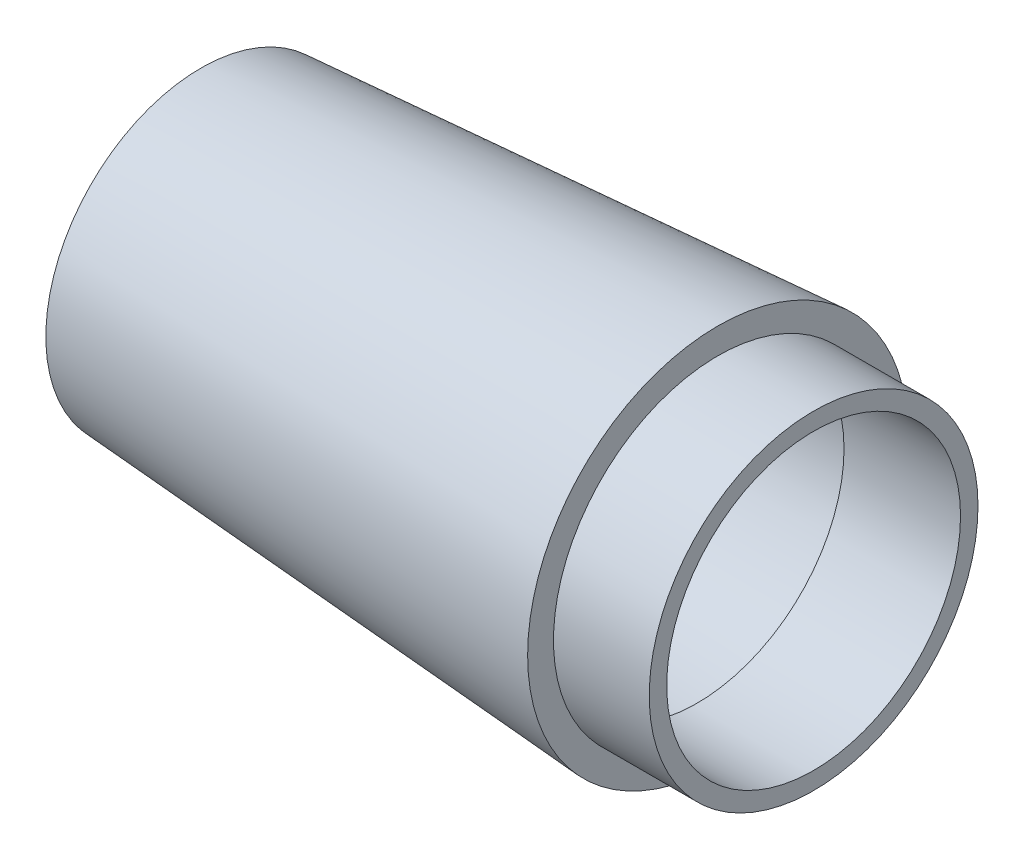
SolidWorks part; units mm, degrees
ref_plane "Front Plane" through (0, 0, 0) normal (0, 0, 1) x (1, 0, 0)
ref_plane "Top Plane" through (0, 0, 0) normal (0, 1, 0) x (1, 0, 0)
ref_plane "Right Plane" through (0, 0, 0) normal (1, 0, 0) x (0, 0, -1)
sketch "Sketch1" plane through (0, 0, 0) normal (0, 0, 1) x (1, 0, 0)
  line L0 (-12.065, 7.62) -> (-12.065, 6.35)
  line L1 (44.7264, 0) -> (-69.8413, 0) construction
  line L2 (13.335, 9.3472) -> (13.335, 8.0772)
  line L3 (-12.065, 0) -> (14.2126, 0) construction
  line L4 (-0.8819, 8.3804) -> (-0.8819, 0)
  line L5 (13.335, 9.3472) -> (-12.065, 7.62)
  line L6 (-12.065, 6.35) -> (13.335, 8.0772)
  line L7 (-0.8819, 0) -> (0.635, 0)
  line L8 (0.635, 0) -> (0.635, 8.4836)
  line L9 (0.635, 8.4836) -> (-0.8819, 8.3804)
  line L11 (18.0075, 7.2191) -> (12.3151, 7.2191)
  line L12 (12.3151, 7.2191) -> (12.3151, 8.0078)
  line L13 (12.3151, 8.0078) -> (13.335, 8.0772)
  line L14 (13.335, 8.0772) -> (18.0397, 8.0772)
  line L15 (18.0397, 7.2191) -> (18.0075, 7.2191)
  line L16 (18.0397, 8.0772) -> (18.0397, 7.2191)
  dimension "D1" = 25.4
  dimension "D2" = 1.27
  dimension "D3" = 7.62
  dimension "D4" = 9.3472
  dimension "D5" = 1.27
revolve "Revolve4" add sketch "Sketch1" angle 360 about L1 region at (-6.4735, 7.3652, 0) region at (-0.1216, 3.5811, 0) region at (6.985, 8.2804, 0)
sketch "Sketch2" plane through (0.635, 0, 0) normal (1, 0, 0) x (0, 0, -1)
  line L3 (-0.3129, 0) -> (0.3129, 0)
  line L4 (-0.3129, 0) -> (-0.3129, 1.0082)
  line L5 (-0.3129, 1.0082) -> (0.3129, 1.0082)
  line L6 (0.3129, 0) -> (0.3129, 1.0082)
  line L9 (-0.3129, 1.0082) -> (0.3129, 1.0082)
  line L10 (-0.3129, 1.0082) -> (-0.3129, 0.7863)
  line L11 (-0.3129, 0.7863) -> (0.3129, 0.7863)
  line L12 (0.3129, 1.0082) -> (0.3129, 0.7863)
  point P3 (0, 0)
  point P8 (0, 0)
revolve "Revolve5" add sketch "Sketch2" angle 180 about L3 region at (0.635, 0.8972, 0)
